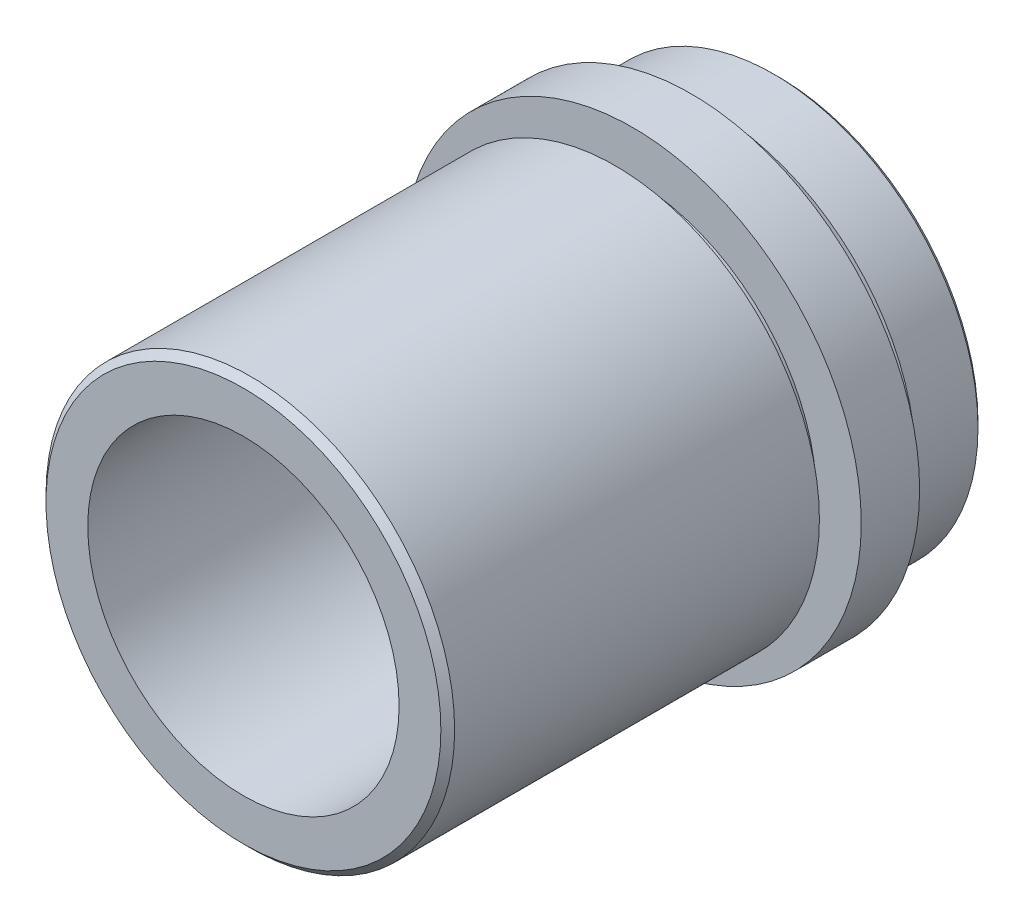
SolidWorks part; units mm, degrees
ref_plane "Płaszczyzna przednia" through (0, 0, 0) normal (0, 0, 1) x (1, 0, 0)
ref_plane "Płaszczyzna górna" through (0, 0, 0) normal (0, 1, 0) x (1, 0, 0)
ref_plane "Płaszczyzna prawa" through (0, 0, 0) normal (1, 0, 0) x (0, 0, -1)
sketch "Szkic1" plane through (0, 0, 0) normal (1, 0, 0) x (0, 0, -1)
  line L0 (-15, 0) -> (-15, 23.5)
  line L1 (-15, 23.5) -> (-9, 23.5)
  line L2 (-9, 23.5) -> (-9, 0)
  line L3 (-9, 0) -> (-15, 0)
  line L4 (-9, 0) -> (-15, 0) construction
sketch "Szkic2" plane through (0, 0, 0) normal (1, 0, 0) x (0, 0, -1)
  line L0 (-55, 0) -> (-55, 21)
  line L1 (-55, 21) -> (-15, 21)
  line L2 (-15, 21) -> (-15, 0)
  line L3 (-15, 0) -> (-55, 0)
  line L4 (-15, 0) -> (-55, 0) construction
sketch "Szkic3" plane through (0, 0, 0) normal (1, 0, 0) x (0, 0, -1)
  line L0 (-55, 20.2929) -> (-54.2929, 21)
  line L1 (-54.2929, 21) -> (-55, 21)
  line L2 (-55, 21) -> (-55, 20.2929)
  line L3 (-15, 0) -> (-55, 0) construction
sketch "Szkic4" plane through (0, 0, 0) normal (1, 0, 0) x (0, 0, -1)
  line L0 (-16.8, 21) -> (-16.8, 18.9)
  line L1 (-16.8, 18.9) -> (-15, 18.9)
  line L2 (-15, 18.9) -> (-15, 21)
  line L3 (-15, 21) -> (-16.8, 21)
  line L4 (-15, 0) -> (-55, 0) construction
ref_plane "Płaszczyzna1" through (0, 0, 9) normal (0, 0, 1) x (1, 0, 0)
ref_plane "Płaszczyzna2" through (0, 0, 55) normal (0, 0, 1) x (1, 0, 0)
sketch "Szkic5" plane through (0, 0, 0) normal (1, 0, 0) x (0, 0, -1)
  line L0 (-9, 0) -> (-9, 21)
  line L1 (-9, 21) -> (0, 21)
  line L2 (0, 21) -> (0, 0)
  line L3 (0, 0) -> (-9, 0)
  line L4 (0, 0) -> (-9, 0) construction
sketch "Szkic6" plane through (0, 0, 0) normal (1, 0, 0) x (0, 0, -1)
  line L0 (-55, 0) -> (-55, 16)
  line L1 (-55, 16) -> (-1, 16)
  line L2 (-1, 16) -> (0, 17)
  line L3 (0, 17) -> (0, 0)
  line L4 (0, 0) -> (-55, 0)
  line L5 (0, 0) -> (-55, 0) construction
sketch "Szkic7" plane through (0, 0, 0) normal (1, 0, 0) x (0, 0, -1)
  line L0 (-0.5, 21) -> (0, 20.5)
  line L1 (0, 20.5) -> (0, 21)
  line L2 (0, 21) -> (-0.5, 21)
  line L3 (0, 0) -> (-9, 0) construction
sketch "Szkic8" plane through (0, 0, 0) normal (1, 0, 0) x (0, 0, -1)
  line L0 (-9, 18.9) -> (-6.9, 18.9)
  line L1 (-6.9, 18.9) -> (-6.9, 21)
  line L2 (-6.9, 21) -> (-9, 21)
  line L3 (-9, 21) -> (-9, 18.9)
  line L4 (0, 0) -> (-9, 0) construction
revolve "Obrót1" add sketch "Szkic1" angle 360 about L4 reverse direction yes
revolve "Obrót2" add sketch "Szkic2" angle 360 about L4 reverse direction yes
revolve "Wycięcie-obrót1" cut sketch "Szkic3" angle 360 about L3 reverse direction yes
revolve "Wycięcie-obrót2" cut sketch "Szkic4" angle 360 about L4 reverse direction yes
revolve "Obrót3" add sketch "Szkic5" angle 360 about L4 reverse direction yes
revolve "Wycięcie-obrót3" cut sketch "Szkic6" angle 360 about L5 reverse direction yes
revolve "Wycięcie-obrót4" cut sketch "Szkic7" angle 360 about L3 reverse direction yes
revolve "Wycięcie-obrót5" cut sketch "Szkic8" angle 360 about L4 reverse direction yes
ref_plane "IP1 XY" through (0, 0, 9) normal (0, 0, 1) x (1, 0, 0)
ref_plane "IP1 XZ" through (0, 0, 0) normal (0, -1, 0) x (-1, 0, 0)
ref_plane "IP1 YZ" through (0, 0, 0) normal (1, 0, 0) x (0, 0, -1)
ref_axis "IP1 X" through (-80.9, 0, 9) along (1, 0, 0)
ref_axis "IP1 Y" through (0, -50, 9) along (0, 1, 0)
ref_axis "IP1 Z" through (0, 0, 80.9) along (0, 0, -1)
sketch3d "IP1"
  point P0 (0, 0, 9)
ref_plane "IP2 XY" through (0, 0, 55) normal (0, 0, 1) x (1, 0, 0)
ref_plane "IP2 XZ" through (0, 0, 0) normal (0, -1, 0) x (-1, 0, 0)
ref_plane "IP2 YZ" through (0, 0, 0) normal (1, 0, 0) x (0, 0, -1)
ref_axis "IP2 X" through (-80.9, 0, 55) along (1, 0, 0)
ref_axis "IP2 Y" through (0, -50, 55) along (0, 1, 0)
ref_axis "IP2 Z" through (0, 0, 80.9) along (0, 0, -1)
sketch3d "IP2"
  point P0 (0, 0, 55)
ref_plane "IP3 XY" through (0, 0, 0) normal (0, 0, 1) x (1, 0, 0)
ref_plane "IP3 XZ" through (0, 0, 0) normal (0, -1, 0) x (-1, 0, 0)
ref_plane "IP3 YZ" through (0, 0, 0) normal (1, 0, 0) x (0, 0, -1)
ref_axis "IP3 X" through (-80.9, 0, 0) along (1, 0, 0)
ref_axis "IP3 Y" through (0, -50, 0) along (0, 1, 0)
ref_axis "IP3 Z" through (0, 0, 80.9) along (0, 0, -1)
sketch3d "IP3"
  point P0 (0, 0, 0)
